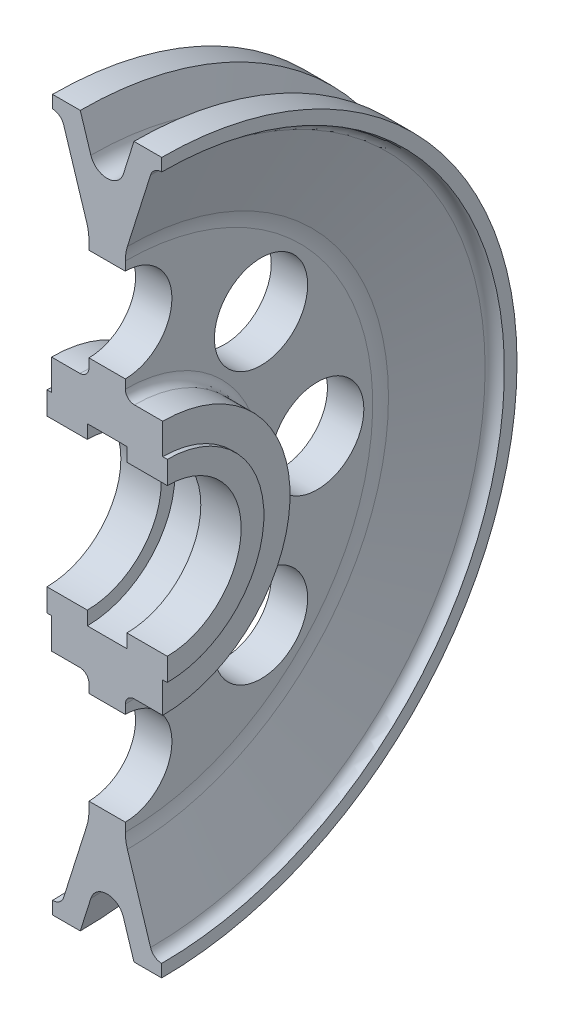
SolidWorks part; units mm, degrees
ref_plane "Piano frontale" through (0, 0, 0) normal (0, 0, 1) x (1, 0, 0)
ref_plane "Piano superiore" through (0, 0, 0) normal (0, 1, 0) x (1, 0, 0)
ref_plane "Piano destro" through (0, 0, 0) normal (1, 0, 0) x (0, 0, -1)
sketch "Sketch1" plane through (0, 0, 0) normal (0, 0, 1) x (1, 0, 0)
  line L0 (-62.2549, -192.8871) -> (72.6149, -192.8871) construction
  line L1 (0, -192.8871) -> (0, 154.8776) construction
  line L2 (35.3511, 156.8497) -> (0, 44.7302) construction
  line L3 (14.3058, 90.1023) -> (23.6104, 119.6129)
  line L4 (23.6104, 119.6129) -> (48, 119.6129)
  line L5 (38.2212, 101.3202) -> (17.8513, 36.7152)
  line L6 (16, 24.687) -> (16, -72.8871)
  line L7 (24, -80.8871) -> (48.9, -80.8871)
  line L8 (48.9, -80.8871) -> (48.9, -115.8871)
  line L9 (48.9, -115.8871) -> (0, -115.8871)
  line L10 (48, 119.6129) -> (48, 108.4903)
  line L11 (0, 79.6129) -> (0, -115.8871)
  circle A0 centre (0, 94.6129) radius 15 construction
  arc A1 (0, 79.6129) -> (14.3058, 90.1023) centre (0, 94.6129) ccw
  arc A3 (48, 108.4903) -> (38.2212, 101.3202) centre (48, 98.237) ccw
  arc A4 (16, -72.8871) -> (24, -80.8871) centre (24, -72.8871) ccw
  arc A5 (16, 24.687) -> (17.8513, 36.7152) centre (56, 24.687) cw
  dimension "D2" = 17.5
  dimension "D3" = 48
  dimension "D4" = 40
  dimension "D5" = 272.5
  dimension "D1" = 30
  dimension "D8" = 8
  dimension "D9" = 40
  dimension "D6" = 77
  dimension "D7" = 16
  dimension "D10" = 35
  dimension "D11" = 48.9
revolve "Puleggia" add sketch "Sketch1" angle 360 about L0
ref_axis "Axis1" through (48.9, -192.8871, 0) along (-1, 0, 0)
mirror "Mirror" about plane through (0, 79.6129, 0) normal (1, 0, 0) of "Puleggia"
sketch "Sketch2" plane through (0, 0, 0) normal (1, 0, 0) x (0, 0, -1)
  line L0 (0, -192.6685) -> (0, -72.8871) construction
  line L1 (0, -72.8871) -> (0, -24.1001) construction
  line L3 (0, -24.1001) -> (0, 24.687) construction
  circle A0 centre (0, -24.1001) radius 41
  circle A1 centre (0, -192.8871) radius 120 construction
  circle A2 centre (0, -192.8871) radius 217.5741 construction
  dimension "D2" = 82
extrude "Foro" cut sketch "Sketch2" against normal blind 120 from offset 60
pattern_circular "PatternFori" count 8 over 360 about axis through (48.9, -192.8871, 0) along (-1, 0, 0) of "Foro"
sketch "Sketch3" plane through (0, 0, 0) normal (0, 0, 1) x (1, 0, 0)
  line L0 (48.9, -115.8871) -> (48.9, -107.8871)
  line L1 (48.9, -107.8871) -> (52.9, -107.8871)
  line L2 (52.9, -107.8871) -> (52.9, -127.8871)
  line L3 (52.9, -127.8871) -> (48.2033, -127.8871)
  line L4 (48.2033, -127.8871) -> (17.4, -127.8871)
  line L5 (17.4, -127.8871) -> (17.4, -115.8871)
  line L6 (17.4, -115.8871) -> (48.9, -115.8871)
  point P9 (0, 0)
  dimension "D1" = 4
  dimension "D2" = 31.5
  dimension "D3" = 12
  dimension "D4" = 8
revolve "Revolve1" add sketch "Sketch3" angle 360 about axis through (48.9, -192.8871, 0) along (-1, 0, 0)
mirror "Mirror1" about plane through (0, 0, 0) normal (1, 0, 0) of "Revolve1"
sketch "Sketch4" plane through (0, 0, 0) normal (0, 1, 0) x (1, 0, 0)
  line L1 (234.8582, 0) -> (-373.7375, 0)
  line L2 (234.8582, 0) -> (234.8582, -358.4503)
  line L3 (234.8582, -358.4503) -> (-373.7375, -358.4503)
  line L4 (-373.7375, 0) -> (-373.7375, -358.4503)
extrude "Cut-Extrude1" cut sketch "Sketch4" against normal through all both and the other way through all
sketch "Sketch5" plane through (0, 0, 0) normal (1, 0, 0) x (0, 0, -1)
  line L0 (-353.6906, -192.8871) -> (592.771, -192.8871)
split line "Split Line1"
